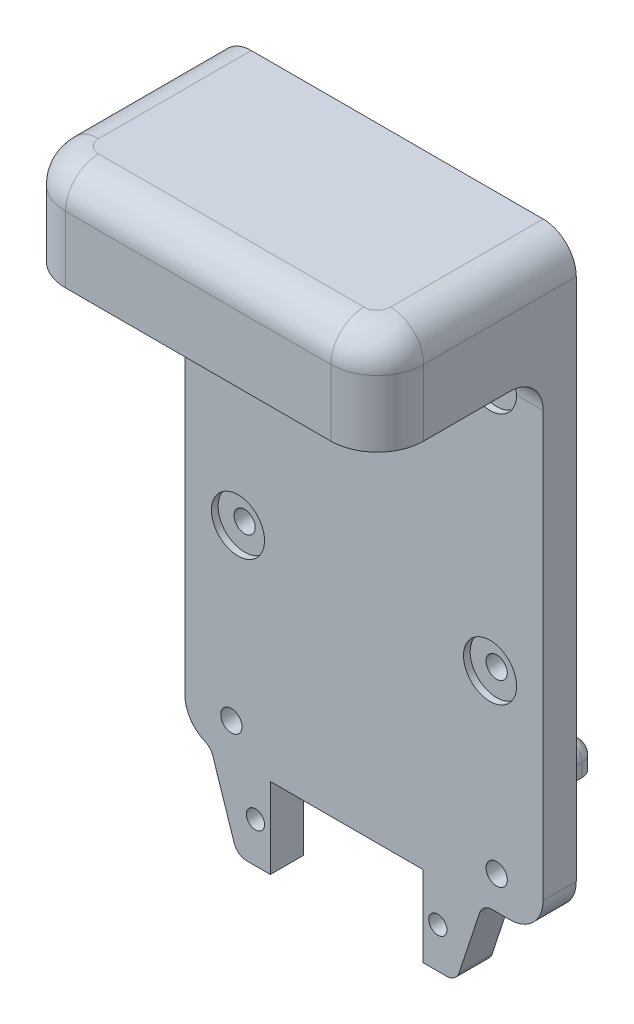
SolidWorks part; units mm, degrees
material "ABS"
ref_plane "前视基准面" through (0, 0, 0) normal (0, 0, 1) x (1, 0, 0)
ref_plane "上视基准面" through (0, 0, 0) normal (0, 1, 0) x (1, 0, 0)
ref_plane "右视基准面" through (0, 0, 0) normal (1, 0, 0) x (0, 0, -1)
other "Configuration Table"
sketch "草图1" plane through (0, 0, 0) normal (0, 0, 1) x (1, 0, 0)
  line L0 (0, -1000) -> (0, 49000) construction
  line L1 (-19, -19) -> (19, -19) construction
  line L2 (-19, -19) -> (-19, 19) construction
  line L3 (-19, 19) -> (19, 19) construction
  line L4 (19, -19) -> (19, 19) construction
  line L5 (-19, -19) -> (19, 19) construction
  line L6 (-19, 19) -> (19, -19) construction
  line L16 (-27, -50) -> (-23.12, -50)
  line L17 (-27, -50) -> (-27, 39)
  line L18 (-27, 39) -> (27, 39)
  line L19 (27, -50) -> (27, 39)
  line L20 (-19.12, -62.15) -> (-14.12, -62.15)
  line L21 (-14.12, -62.15) -> (-14.12, -50)
  line L25 (-2.62, -50) -> (-2.62, -73.1982) construction
  line L26 (8.88, -62.15) -> (8.88, -50)
  line L27 (-23.12, -50) -> (-14.12, -50) construction
  line L28 (-14.12, -50) -> (8.88, -50)
  line L29 (13.88, -62.15) -> (8.88, -62.15)
  line L31 (8.88, -50) -> (17.88, -50) construction
  line L32 (13.88, -62.15) -> (17.88, -50)
  line L33 (-19.12, -62.15) -> (-23.12, -50)
  line L34 (-32.24, -50) -> (-23.12, -50) construction
  line L35 (17.88, -50) -> (27, -50)
  circle A0 centre (-19, 19) radius 1.6
  circle A1 centre (19, 19) radius 1.6
  circle A2 centre (19, -19) radius 1.6
  circle A3 centre (-19, -19) radius 1.6
  circle A8 centre (-20, -45) radius 1.6
  circle A10 centre (20, -45) radius 1.6
  circle A11 centre (-16.37, -56.075) radius 1.375
  circle A12 centre (11.13, -56.075) radius 1.375
  point P0 (0, 0)
  point P7 (0, 0)
  point P11 (0, 0)
  point P13 (0, 0)
  point P23 (0, 39)
  point P40 (-14.12, -56.075)
  dimension "D3" = 3.2
  dimension "D5" = 50
  dimension "D4" = 39
  dimension "D6" = 3.2
  dimension "D7" = 40
  dimension "D8" = 5
  dimension "D13" = 27.5
  dimension "D14" = 2.75
  dimension "D1" = 38
  dimension "D2" = 54
  dimension "D9" = 5
  dimension "D10" = 12.15
  dimension "D11" = 2.62
  dimension "D12" = 23
  dimension "D15" = 4
extrude "凸台-拉伸1" add sketch "草图1" along normal blind 5
sketch "草图2" plane through (0, 0, 5) normal (0, 0, 1) x (1, 0, 0)
  line L5 (27, -50) -> (27, 39) construction
  line L10 (-27, 39) -> (27, 39)
  line L11 (-27, 39) -> (-27, 24)
  line L12 (-27, 24) -> (27, 24)
  line L13 (27, 39) -> (27, 24)
  dimension "D1" = 15
extrude "凸台-拉伸2" add sketch "草图2" along normal blind 25
sketch "草图3" plane through (0, 24, 0) normal (0, -1, 0) x (1, 0, 0)
  line L0 (0, -976) -> (0, 49024) construction
  line L1 (-27, 30) -> (27, 30) construction
  line L2 (-27, 5) -> (-23.12, 5) construction
  circle A0 centre (-20, 23) radius 3
  circle A1 centre (20, 23) radius 3
  point P5 (0, 30)
  dimension "D1" = 40
  dimension "D2" = 18
extrude "切除-拉伸1" cut sketch "草图3" against normal blind 10
fillet "圆角1" radius 7 2 edges at (27, 31.5, 30) (-27, 31.5, 30)
fillet "圆角2" radius 5 5 edges at (27, 39, 11.5) (24.9497, 39, 27.9497) (-27, 39, 11.5) (-24.9497, 39, 27.9497) (0, 39, 30)
fillet "圆角3" radius 5 1 edges at (0, 24, 5)
chamfer "倒角1" distance 0.5 angle 45 2 edges at (20, 24, 26) (-20, 24, 20)
sketch "草图4" plane through (0, 0, 5) normal (0, 0, 1) x (1, 0, 0)
  circle A0 centre (-19, 19) radius 4
  circle A1 centre (19, 19) radius 4
  circle A2 centre (-19, -19) radius 4
  circle A3 centre (19, -19) radius 4
  point P7 (-19, -19)
  point P11 (19, 19)
  dimension "D1" = 8
extrude "切除-拉伸2" cut sketch "草图4" against normal blind 1 and the other way through all
fillet "圆角4" radius 5 2 edges at (-27, -50, 2.5) (27, -50, 2.5)
sketch "草图5" plane through (0, 0, 0) normal (0, 0, -1) x (-1, 0, 0)
  line L0 (14.12, -50) -> (-8.88, -50) construction
  line L1 (14.12, -50) -> (-8.88, -50) construction
  line L2 (2.62, -1047.5) -> (2.62, 48952.5) construction
  line L4 (14.12, -46) -> (-8.88, -46)
  line L5 (14.12, -46) -> (14.12, -50)
  line L6 (14.12, -50) -> (-8.88, -50)
  line L7 (-8.88, -46) -> (-8.88, -50)
  line L8 (14.12, -46) -> (-8.88, -50) construction
  line L9 (14.12, -50) -> (-8.88, -46) construction
  point P3 (2.62, -48)
  point P5 (2.62, -50)
  dimension "D1" = 4
  dimension "D2" = 23
extrude "凸台-拉伸3" add sketch "草图5" along normal blind 21
fillet "圆角5" radius 2 9 edges at (8.88, -46, -10.5) (-2.62, -46, -21) (-14.12, -46, -10.5) (8.88, -48, -21) (-14.12, -48, -21) (17.88, -50, 2.5) (-23.12, -50, 2.5) (-19.12, -62.15, 2.5) (13.88, -62.15, 2.5)
fillet "圆角6" radius 3 5 edges at (-14.12, -49, 0) (-13.5342, -46.5858, 0) (8.88, -49, 0) (8.2942, -46.5858, 0) (-2.62, -46, 0)
sketch "草图6" plane through (0, 0, 0) normal (0, 0, 1) x (1, 0, 0)
  circle A0 centre (-20, -45) radius 3.25
  circle A1 centre (20, -45) radius 3.25
extrude "切除-拉伸3" cut sketch "草图6" along normal blind 1 and the other way through all
